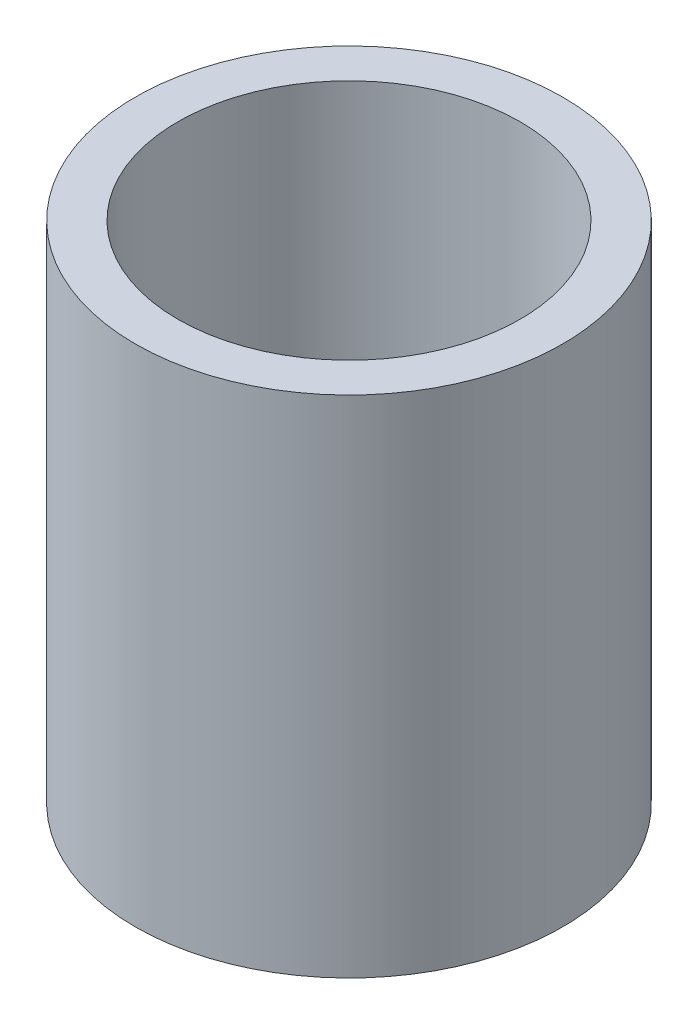
SolidWorks part; units mm, degrees
ref_plane "Front Plane" through (0, 0, 0) normal (0, 0, 1) x (1, 0, 0)
ref_plane "Top Plane" through (0, 0, 0) normal (0, 1, 0) x (1, 0, 0)
ref_plane "Right Plane" through (0, 0, 0) normal (1, 0, 0) x (0, 0, -1)
sketch "Sketch1" plane through (0, 0, 0) normal (0, 1, 0) x (1, 0, 0)
  circle A0 centre (0, 0) radius 27.5
  dimension "SLEEVE_OD" = 55
extrude "Boss-Extrude1" add sketch "Sketch1" along normal blind 64.948
sketch "Sketch2" plane through (0, 0, 0) normal (0, 1, 0) x (1, 0, 0)
  circle A0 centre (0, 0) radius 22.0153
  dimension "BORE_D" = 44.0306
extrude "Cut-Extrude1" cut sketch "Sketch2" along normal through all
chamfer "Chamfer1" distance 3.7968 angle 30 rebuild error yes
